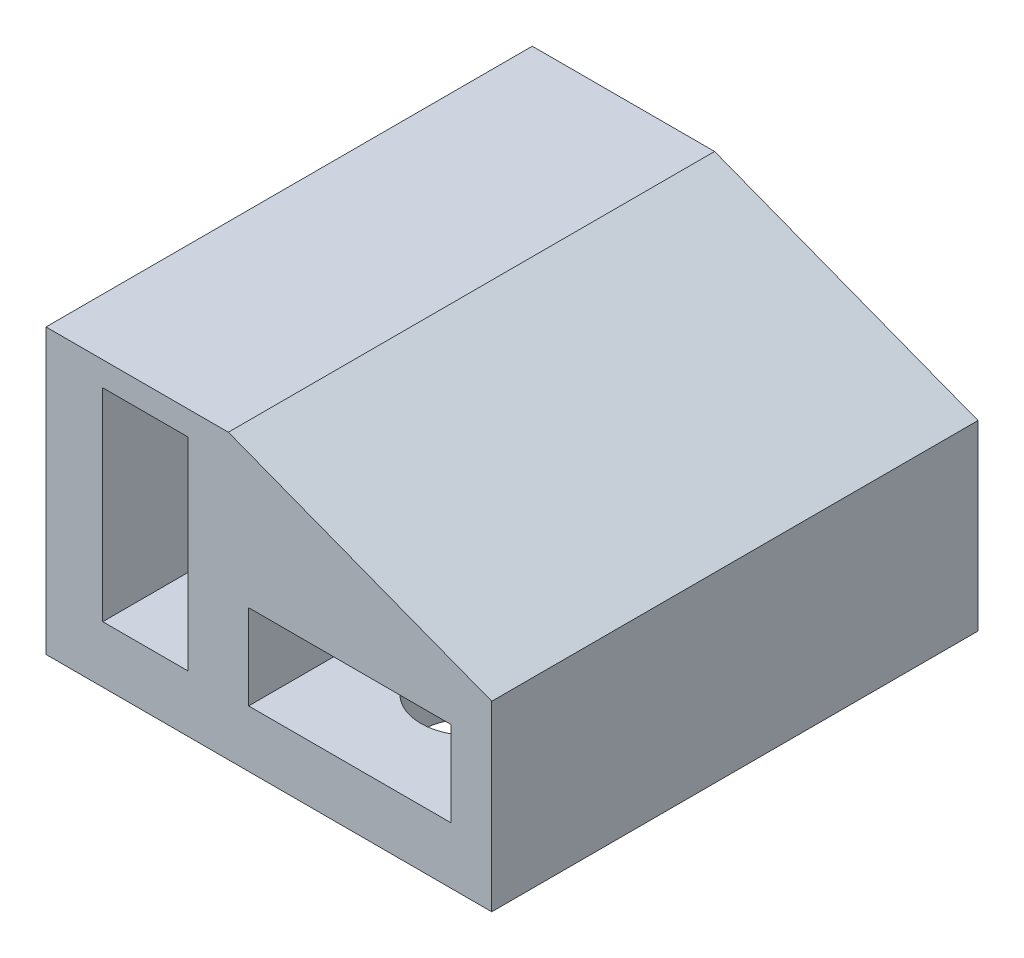
SolidWorks part; units mm, degrees
ref_plane "Front Plane" through (0, 0, 0) normal (0, 0, 1) x (1, 0, 0)
ref_plane "Top Plane" through (0, 0, 0) normal (0, 1, 0) x (1, 0, 0)
ref_plane "Right Plane" through (0, 0, 0) normal (1, 0, 0) x (0, 0, -1)
sketch "Sketch1" plane through (0, 0, 0) normal (0, 0, 1) x (1, 0, 0)
  line L0 (0, 0) -> (0, 7)
  line L1 (0, 0) -> (11, 0)
  line L2 (0, 7) -> (4.5, 7)
  line L3 (11, 0) -> (11, 4.5)
  line L4 (4.5, 7) -> (11, 4.5)
  dimension "D1" = 7
  dimension "D2" = 11
  dimension "D3" = 4.5
  dimension "D4" = 4.5
extrude "Boss-Extrude1" add sketch "Sketch1" along normal blind 12
sketch "Sketch2" plane through (0, 0, 0) normal (-1, 0, 0) x (0, 0, 1)
  line L0 (4.4434, 6.4) -> (4.4434, 1.4)
  line L1 (0, 0) -> (3, 0)
  line L2 (0, 0) -> (0, 3.9)
  line L3 (0, 3.9) -> (3, 3.9)
  line L4 (3, 0) -> (3, 3.9)
  line L5 (5.8868, 3.9) -> (4.4434, 6.4)
  line L6 (4.4434, 6.4) -> (1.5566, 6.4)
  line L7 (1.5566, 6.4) -> (0.1132, 3.9)
  line L8 (0.1132, 3.9) -> (1.5566, 1.4)
  line L9 (1.5566, 1.4) -> (4.4434, 1.4)
  line L10 (4.4434, 1.4) -> (5.8868, 3.9)
  line L11 (7.5566, 6.4) -> (7.5566, 1.4)
  line L12 (12, 0) -> (9, 0)
  line L13 (12, 0) -> (12, 3.9)
  line L14 (12, 3.9) -> (9, 3.9)
  line L15 (9, 0) -> (9, 3.9)
  line L16 (6.1132, 3.9) -> (7.5566, 1.4)
  line L17 (7.5566, 1.4) -> (10.4434, 1.4)
  line L18 (10.4434, 1.4) -> (11.8868, 3.9)
  line L19 (11.8868, 3.9) -> (10.4434, 6.4)
  line L20 (10.4434, 6.4) -> (7.5566, 6.4)
  line L21 (7.5566, 6.4) -> (6.1132, 3.9)
  line L22 (1.5566, 6.4) -> (0, 6.4)
  line L23 (0, 7) -> (0, 0) construction
  line L24 (1.5566, 1.4) -> (0, 1.4)
  line L25 (10.4434, 6.4) -> (12, 6.4)
  line L26 (12, 7) -> (12, 0) construction
  line L27 (10.4434, 1.4) -> (12, 1.4)
  circle A0 centre (3, 3.9) radius 2.5 construction
  circle A1 centre (9, 3.9) radius 2.5 construction
  line M3 (0, 7) -> (0, 0)
  line M5 (12, 0) -> (12, 7)
  dimension "D1" = 3
  dimension "D2" = 3.9
  dimension "D3" = 5
  dimension "D4" = 3
  dimension "D5" = 3.9
  dimension "D6" = 5
extrude "Cut-Extrude1" cut sketch "Sketch2" against normal blind 3.5 contours L4 L9 L0 L6 L7 L3 | L0 L10 L5 | L19 L20 L11 L17 L15 L14 | L17 L18 L14 L15 | L8 L9 L4 L3 | L11 L21 L16 | L7 L22 L3 M3 | L24 L8 L3 M3 | L25 L19 L14 M5 | L18 L27 L13 L14 region at (0, 3.9, 4.9245) region at (0, 4.3762, 2.9313) region at (0, 5.5102, 0.5214) region at (0, 2.7889, 1.8774) region at (0, 2.2898, 0.5214) region at (0, 4.3762, 9.0687) region at (0, 3.9, 7.0755) region at (0, 5.5102, 11.4786) region at (0, 2.7889, 10.1226) region at (0, 2.2898, 11.4786)
sketch "Sketch3" plane through (0, 7, 0) normal (0, 1, 0) x (1, 0, 0)
  line L0 (4.5, -12) -> (0, -12) construction
  line L1 (0, 0) -> (1.4, 0)
  line L2 (0, 0) -> (0, -12)
  line L3 (0, -12) -> (1.4, -12)
  line L4 (1.4, 0) -> (1.4, -12)
  dimension "D1" = 1.4
extrude "Boss-Extrude2" add sketch "Sketch3" against normal blind 7
sketch "Sketch4" plane through (0, 0, 0) normal (0, -1, 0) x (1, 0, 0)
  line L0 (10, 7.5566) -> (5, 7.5566)
  line L1 (11, 12) -> (7.5, 12)
  line L2 (11, 12) -> (11, 9)
  line L3 (11, 9) -> (7.5, 9)
  line L4 (7.5, 12) -> (7.5, 9)
  line L5 (7.5, 6.1132) -> (10, 7.5566)
  line L6 (10, 7.5566) -> (10, 10.4434)
  line L7 (10, 10.4434) -> (7.5, 11.8868)
  line L8 (7.5, 11.8868) -> (5, 10.4434)
  line L9 (5, 10.4434) -> (5, 7.5566)
  line L10 (5, 7.5566) -> (7.5, 6.1132)
  line L11 (5, 4.4434) -> (10, 4.4434)
  line L12 (11, 0) -> (7.5, 0)
  line L13 (11, 0) -> (11, 3)
  line L14 (11, 3) -> (7.5, 3)
  line L15 (7.5, 0) -> (7.5, 3)
  line L16 (7.5, 5.8868) -> (5, 4.4434)
  line L17 (5, 4.4434) -> (5, 1.5566)
  line L18 (5, 1.5566) -> (7.5, 0.1132)
  line L19 (7.5, 0.1132) -> (10, 1.5566)
  line L20 (10, 1.5566) -> (10, 4.4434)
  line L21 (10, 4.4434) -> (7.5, 5.8868)
  line L22 (5, 1.5566) -> (5, 0)
  line L23 (0, 0) -> (11, 0) construction
  line L24 (10, 1.5566) -> (10, 0)
  line L25 (5, 10.4434) -> (5, 12)
  line L26 (0, 12) -> (11, 12) construction
  line L27 (10, 10.4434) -> (10, 12)
  circle A0 centre (7.5, 9) radius 2.5 construction
  circle A1 centre (7.5, 3) radius 2.5 construction
  circle A2 centre (7.5, 9) radius 1.25
  circle A3 centre (7.5, 3) radius 1.25
  line M1 (0, 0) -> (11, 0)
  line M3 (11, 12) -> (0, 12)
  dimension "D7" = 2.5
  dimension "D8" = 2.5
  dimension "D1" = 3
  dimension "D2" = 3.5
  dimension "D3" = 5
  dimension "D4" = 3.5
  dimension "D5" = 3
  dimension "D6" = 5
extrude "Cut-Extrude2" cut sketch "Sketch4" against normal blind 3.5 contours L7 L27 L1 L4 | L8 L9 L0 L6 L3 L4 | L6 L7 L4 L3 | L11 L21 L16 | L19 L20 L14 L15 | L18 L22 L15 M1 | L24 L19 L15 M1 | L14 L20 L11 L17 L18 L15 | L0 L10 L5 | L25 L8 L4 M3 | L5 L6 L7 L8 L9 L10 region at (7.5, 0, 7.0755) region at (7.5, 0, 7.6228) region at (8.7813, 0, 10.2962) region at (5.8898, 0, 11.4786) region at (9.1102, 0, 11.4786) region at (7.5, 0, 4.9245) region at (7.5, 0, 4.3772) region at (5.8898, 0, 0.5214) region at (8.7813, 0, 1.7038) region at (9.1102, 0, 0.5214)
sketch "Sketch5" plane through (0, 0, 0) normal (0, 0, -1) x (-1, 0, 0)
  line L1 (-11, 0) -> (-4, 0)
  line L2 (-11, 0) -> (-11, 1.4)
  line L3 (-11, 1.4) -> (-4, 1.4)
  line L4 (-4, 0) -> (-4, 1.4)
  dimension "D1" = 7
  dimension "D2" = 1.4
extrude "Boss-Extrude3" add sketch "Sketch5" against normal blind 12
sketch "Sketch6" plane through (0, 0, 0) normal (-1, 0, 0) x (0, 0, 1)
  line L1 (0, 0) -> (3.5, 0)
  line L2 (0, 0) -> (0, 3.9)
  line L3 (0, 3.9) -> (3.5, 3.9)
  line L4 (3.5, 0) -> (3.5, 3.9)
  line L5 (12, 0) -> (8.5, 0)
  line L6 (12, 0) -> (12, 3.9)
  line L7 (12, 3.9) -> (8.5, 3.9)
  line L8 (8.5, 0) -> (8.5, 3.9)
  circle A0 centre (3.5, 3.9) radius 1.25
  circle A1 centre (8.5, 3.9) radius 1.25
  dimension "D3" = 2.5
  dimension "D6" = 2.5
  dimension "D1" = 3.9
  dimension "D2" = 3.5
  dimension "D4" = 3.5
  dimension "D5" = 3.9
extrude "Cut-Extrude3" cut sketch "Sketch6" against normal blind 3.5 contours L4 A0 L3 | L3 A0 L4 | L7 A1 L8 | L8 A1 L7 region at (0, 3.3695, 2.9695) region at (0, 4.0768, 3.6768) region at (0, 4.0768, 8.3232) region at (0, 3.3695, 9.0305)
extrude "Cut-Extrude4" cut sketch "Sketch4<3>" against normal blind 3.5 contours L4 A2 L3 | L3 A2 L4 | L14 A3 L15 | L15 A3 L14 region at (7.3232, 0, 8.8232) region at (8.0305, 0, 9.5305) region at (8.0305, 0, 2.4695) region at (7.3232, 0, 3.1768)
sketch "Sketch4<3>" plane through (0, 0, 0) normal (0, -1, 0) x (1, 0, 0) same geometry as "Sketch4"
